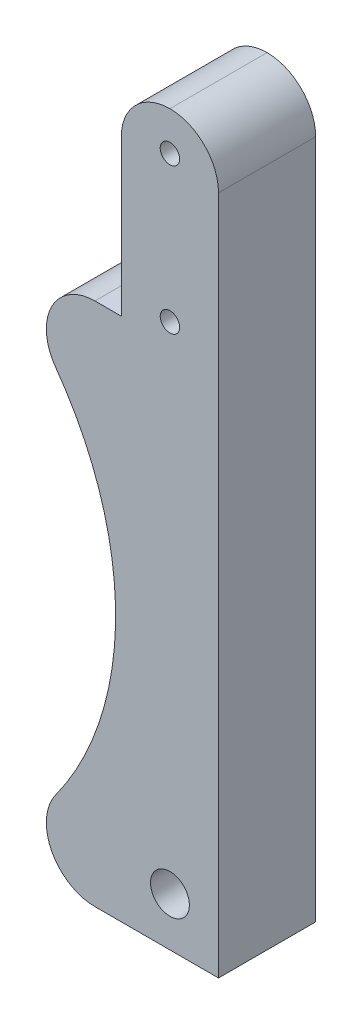
SolidWorks part; units mm, degrees
ref_plane "Front" through (0, 0, 0) normal (0, 0, 1) x (1, 0, 0)
ref_plane "Top" through (0, 0, 0) normal (0, 1, 0) x (1, 0, 0)
ref_plane "Right" through (0, 0, 0) normal (1, 0, 0) x (0, 0, -1)
sketch "Esquisse1" plane through (0, 0, 0) normal (0, 0, 1) x (1, 0, 0)
  line L1 (0, 0) -> (10, 0)
  line L2 (0, 0) -> (0, 75)
  line L3 (0, 75) -> (10, 75)
  line L4 (10, 0) -> (10, 75)
  dimension "D1" = 10
  dimension "D2" = 75
extrude "Boss.-Extru.1" add sketch "Esquisse1" along normal blind 10
sketch "Esquisse2" plane through (0, 0, 10) normal (0, 0, 1) x (1, 0, 0)
  line L0 (5, 75) -> (5, 56) construction
  line L1 (10, 75) -> (0, 75) construction
  line L2 (0, 0) -> (10, 0) construction
  line L3 (5, 5) -> (5, 0) construction
  circle A0 centre (5, 56) radius 1
  circle A1 centre (5, 71) radius 1
  circle A2 centre (5, 5) radius 2
  point P11 (5, 0)
  dimension "D1" = 15
  dimension "D2" = 4
  dimension "D3" = 2
  dimension "D4" = 4
  dimension "D5" = 5
extrude "Enlèv. mat.-Extru.1" cut sketch "Esquisse2" against normal up to vertex (10 mm away) up to point (0, 75, 0)
fillet "Congé1" radius 5 2 edges at (10, 75, 5) (0, 75, 5)
sketch "Esquisse3" plane through (0, 0, 10) normal (0, 0, 1) x (1, 0, 0)
  line L0 (0, 0) -> (-15, 0)
  line L1 (0, 0) -> (0, 54)
  line L2 (0, 70) -> (0, 0) construction
  line L3 (0, 54) -> (-15, 54)
  line L4 (-15, 0) -> (-15, 54) construction
  arc A0 (-15, 54) -> (-15, 0) centre (-33.0901, 27) cw
  dimension "D1" = 32.5
  dimension "D3" = 15
  dimension "D2" = 54
extrude "Boss.-Extru.2" add sketch "Esquisse3" against normal up to vertex (10 mm away) up to point (0, 0, 0)
fillet "Congé2" radius 5 2 edges at (-15, 54, 5) (-15, 0, 5)
